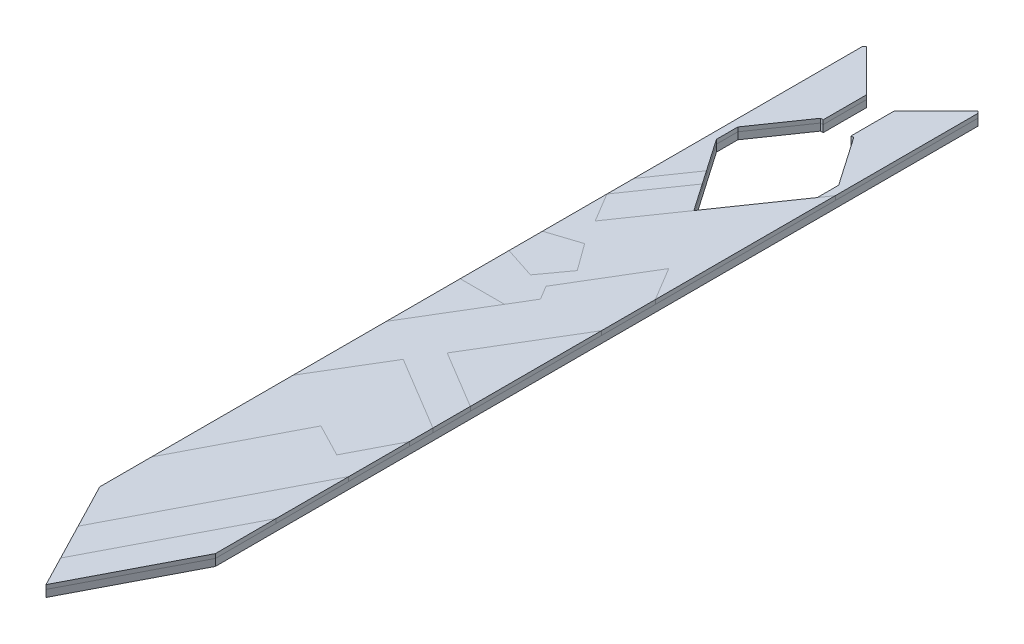
SolidWorks part; units mm, degrees
ref_plane "前视基准面" through (0, 0, 0) normal (0, 0, 1) x (1, 0, 0)
ref_plane "上视基准面" through (0, 0, 0) normal (0, 1, 0) x (1, 0, 0)
ref_plane "右视基准面" through (0, 0, 0) normal (1, 0, 0) x (0, 0, -1)
sketch "草图1" plane through (0, 0, 0) normal (0, 1, 0) x (1, 0, 0)
  line L0 (-40, 0) -> (40, 0) construction
  line L1 (40, 0) -> (0, -40)
  line L2 (0, -40) -> (-40, 0)
  line L3 (-41.46, -540.3) -> (-41.46, -1.46)
  line L4 (-41.46, -540.3) -> (0, -620.29)
  line L5 (-41.46, -1.46) -> (-40, 0)
  line L6 (0, -40) -> (0, -620.29) construction
  line L7 (0, -620.29) -> (0, -540.3) construction
  line L8 (41.46, -540.3) -> (0, -620.29)
  line L9 (41.46, -540.3) -> (41.46, -1.46)
  line L10 (41.46, -1.46) -> (40, 0)
  dimension "D1" = 80
  dimension "D2" = 40
  dimension "D4" = 580.29
  dimension "D5" = 79.99
  dimension "D6" = 82.92
extrude "凸台-拉伸1" add sketch "草图1" along normal blind 5
sketch "草图2" plane through (0, 5, 0) normal (0, 1, 0) x (1, 0, 0)
  line L0 (0, -40) -> (0, -61) construction
  line L1 (0, -61) -> (0, -163.74) construction
  line L2 (11.93, -61) -> (-11.93, -61)
  line L3 (-11.93, -61) -> (-36.16, -96.06)
  line L4 (-36.16, -96.06) -> (-36.16, -111.41)
  line L5 (-36.16, -111.41) -> (0, -163.74)
  line L6 (-36.16, -111.41) -> (36.16, -111.41) construction
  line L7 (-41.46, -1.46) -> (-41.46, -540.3) construction
  line L8 (36.16, -111.41) -> (0, -163.74)
  line L9 (36.16, -96.06) -> (36.16, -111.41)
  line L10 (11.93, -61) -> (36.16, -96.06)
  point P13 (0, -111.41)
  dimension "D1" = 21
  dimension "D2" = 102.74
  dimension "D3" = 11.93
  dimension "D4" = 15.35
  dimension "D5" = 52.33
  dimension "D6" = 5.3
extrude "切除-拉伸1" cut sketch "草图2" against normal up to next
sketch "草图3" plane through (0, 5, 0) normal (0, 1, 0) x (1, 0, 0)
  line L0 (0, -163.74) -> (0, -208.74) construction
  line L1 (0, -208.74) -> (-27, -208.74) construction
  line L2 (-27, -208.74) -> (0, -163.74)
  line L3 (27, -208.74) -> (0, -163.74)
  line L4 (27, -208.74) -> (0, -253.74)
  line L5 (-27, -208.74) -> (0, -253.74)
  line L6 (0, -263.74) -> (0, -273.74) construction
  line L7 (0, -263.74) -> (-6, -263.74) construction
  line L9 (-6, -263.74) -> (0, -273.74)
  line L10 (6, -263.74) -> (0, -273.74)
  line L12 (6, -263.74) -> (0, -253.74)
  line L13 (-6, -263.74) -> (0, -253.74)
  line L14 (0, -163.74) -> (36.16, -111.41) construction
  dimension "D1" = 45
  dimension "D2" = 27
  dimension "D3" = 10
  dimension "D4" = 6
sketch "草图4" plane through (0, 0, 0) normal (0, -1, 0) x (1, 0, 0)
  line L0 (-10, 61) -> (10, 61)
  line L1 (11.93, 61) -> (-11.93, 61) construction
  line L2 (10, 61) -> (10, 30)
  line L3 (40, 0) -> (0, 40) construction
  line L4 (10, 30) -> (-10, 30)
  line L5 (0, 30) -> (0, 61) construction
  line L6 (-10, 61) -> (-10, 30)
  dimension "D1" = 10
extrude "切除-拉伸8" cut sketch "草图4" against normal through all both
sketch "草图5" plane through (0, 0, 0) normal (0, -1, 0) x (1, 0, 0)
  line L0 (-41.46, 540.3) -> (-41.46, 548.3)
  line L1 (-41.46, 548.3) -> (0, 628.29)
  line L2 (0, 628.29) -> (0, 540.3) construction
  line L3 (-41.46, 540.3) -> (0, 620.29) construction
  line L4 (41.46, 548.3) -> (0, 628.29)
  line L5 (41.46, 540.3) -> (41.46, 548.3)
  line L6 (41.46, 540.3) -> (0, 620.29)
  line L7 (0, 620.29) -> (-41.46, 540.3)
  dimension "D1" = 8
extrude "凸台-拉伸2" add sketch "草图5" against normal up to surface (5 mm away) up to face at (0, 5, 143.6939)
sketch "草图6" plane through (0, 5, 0) normal (0, 1, 0) x (1, 0, 0)
  line L0 (0, -163.74) -> (-27, -208.74)
  line L1 (-27, -208.74) -> (0, -253.74)
  line L2 (0, -253.74) -> (27, -208.74)
  line L3 (27, -208.74) -> (0, -163.74)
  line L4 (0, -253.74) -> (-6, -263.74)
  line L5 (-6, -263.74) -> (0, -273.74)
  line L6 (0, -273.74) -> (6, -263.74)
  line L7 (6, -263.74) -> (0, -253.74)
  line L8 (0, -263.74) -> (-6, -263.74) construction
sketch "草图7" plane through (0, 0, 0) normal (0, 1, 0) x (1, 0, 0)
  line L0 (27, -208.74) -> (50, -170.4067)
  line L1 (50, 1.71) -> (-50, 1.71)
  line L2 (50, 1.71) -> (50, -628.29)
  line L3 (50, -628.29) -> (-50, -628.29)
  line L4 (-50, 1.71) -> (-50, -628.29)
  line L5 (0, -273.74) -> (-50, -357.0733)
  line L6 (0, -273.74) -> (6, -263.74) construction
  line L7 (0, -253.74) -> (27, -208.74) construction
  dimension "D1" = 100
  dimension "D2" = 630
sketch "草图8" plane through (0, 0, 0) normal (0, 1, 0) x (1, 0, 0)
  line L1 (-50, 0) -> (50, 0)
  line L2 (-50, 0) -> (-50, -640)
  line L3 (-50, -640) -> (50, -640)
  line L4 (50, 0) -> (50, -640)
  dimension "D1" = 100
  dimension "D2" = 640
sketch "草图9" plane through (0, 5, 0) normal (0, 1, 0) x (1, 0, 0)
  line L0 (6, -263.74) -> (0, -273.74)
  line L1 (-41.46, -409.7055) -> (41.46, -271.5055)
  line L3 (41.46, -452.6841) -> (-41.46, -409.7055)
  line L4 (0, -628.29) -> (0, -340.6055) construction
  line L5 (0, -163.74) -> (41.46, -103.74)
  line L7 (41.46, -184.64) -> (0, -253.74) construction
  line L9 (-41.46, -1.46) -> (-41.46, -548.3) construction
  line L10 (0, -163.74) -> (-28.9032, -205.5681)
  line L14 (0, -253.74) -> (6, -263.74)
  line L15 (27, -208.74) -> (41.46, -232.84)
  line L16 (41.46, -365.4815) -> (0, -340.6055)
  line L18 (0, -628.29) -> (41.46, -548.3)
  line L19 (41.46, -548.3) -> (41.46, -1.46)
  line L20 (41.46, -1.46) -> (40, 0)
  line L21 (40, 0) -> (10, -30)
  line L22 (10, -30) -> (10, -61)
  line L23 (10, -61) -> (11.93, -61)
  line L24 (11.93, -61) -> (36.16, -96.06)
  line L25 (36.16, -96.06) -> (36.16, -111.41)
  line L26 (36.16, -111.41) -> (0, -163.74)
  line L27 (0, -163.74) -> (-36.16, -111.41)
  line L28 (-36.16, -111.41) -> (-36.16, -96.06)
  line L29 (-36.16, -96.06) -> (-11.93, -61)
  line L30 (-11.93, -61) -> (-10, -61)
  line L31 (-10, -61) -> (-10, -30)
  line L32 (-10, -30) -> (-40, 0)
  line L33 (-40, 0) -> (-41.46, -1.46)
  line L34 (-41.46, -1.46) -> (-41.46, -548.3)
  line L35 (-41.46, -548.3) -> (0, -628.29)
  line L36 (0, -628.29) -> (41.46, -548.3)
  line L37 (41.46, -548.3) -> (41.46, -1.46)
  line L38 (41.46, -1.46) -> (40, 0)
  line L39 (40, 0) -> (10, -30)
  line L40 (10, -30) -> (10, -61)
  line L41 (10, -61) -> (11.93, -61)
  line L42 (11.93, -61) -> (36.16, -96.06)
  line L43 (36.16, -96.06) -> (36.16, -111.41)
  line L44 (36.16, -111.41) -> (0, -163.74)
  line L45 (0, -163.74) -> (-36.16, -111.41)
  line L46 (-36.16, -111.41) -> (-36.16, -96.06)
  line L47 (-36.16, -96.06) -> (-11.93, -61)
  line L48 (-11.93, -61) -> (-10, -61)
  line L49 (-10, -61) -> (-10, -30)
  line L50 (-10, -30) -> (-40, 0)
  line L51 (-40, 0) -> (-41.46, -1.46)
  line L52 (-41.46, -1.46) -> (-41.46, -548.3)
  line L53 (-41.46, -548.3) -> (0, -628.29)
  line L55 (-41.46, -184.64) -> (-13.5091, -144.19)
  line L56 (-18.6346, -262.2564) -> (-4.5278, -242.84)
  line L57 (-4.5278, -242.84) -> (-18.6346, -223.4236)
  line L58 (-18.6346, -223.4236) -> (-41.46, -230.84)
  line L59 (-41.46, -230.84) -> (-41.46, -254.84)
  line L60 (-41.46, -254.84) -> (-18.6346, -262.2564)
  line L62 (-41.46, -165.2902) -> (-20.1944, -134.5151)
  line L63 (-27, -208.74) -> (0, -253.74) construction
  line L64 (-9.66, -289.84) -> (-41.46, -289.84)
  line L65 (-28.9032, -205.5681) -> (-41.46, -184.64)
  line L66 (-28.9032, -205.5681) -> (-18.6346, -223.4236)
  line L67 (41.46, -409.2224) -> (-36.043, -558.7512)
  line L70 (0, -431.1948) -> (-41.46, -511.1848)
  line L71 (-41.46, -511.1848) -> (21.3079, -543.7183) construction
  line L72 (-11.2634, -606.5591) -> (41.46, -504.8382)
  line L78 (41.46, -548.3) -> (41.46, -1.46) construction
  line L80 (0, -628.29) -> (0, -532.6741) construction
  line L83 (-24.7796, -580.4821) -> (0, -532.6741)
  line L84 (0, -532.6741) -> (41.46, -452.6841)
  line L95 (-11.8334, -360.3278) -> (41.46, -392.3038)
  line L99 (27, -208.74) -> (41.46, -184.64)
  line L150 (27, -208.74) -> (0, -253.74) construction
  line L151 (0, -273.74) -> (-41.46, -342.84)
  line L152 (6, -263.74) -> (0, -273.74) construction
  line L153 (27, -208.74) -> (0, -163.74)
  line L184 (0, -273.74) -> (-6, -263.74)
  line L185 (-6, -263.74) -> (27, -208.74)
  circle A0 centre (-24.9434, -242.84) radius 16.5166 construction
  line M1 (0, -628.29) -> (41.46, -548.3)
  line M2 (41.46, -548.3) -> (41.46, -1.46)
  line M3 (41.46, -1.46) -> (40, 0)
  line M4 (40, 0) -> (10, -30)
  line M5 (10, -30) -> (10, -61)
  line M6 (10, -61) -> (11.93, -61)
  line M7 (11.93, -61) -> (36.16, -96.06)
  line M8 (36.16, -96.06) -> (36.16, -111.41)
  line M9 (36.16, -111.41) -> (0, -163.74)
  line M10 (0, -163.74) -> (-36.16, -111.41)
  line M11 (-36.16, -111.41) -> (-36.16, -96.06)
  line M12 (-36.16, -96.06) -> (-11.93, -61)
  line M13 (-11.93, -61) -> (-10, -61)
  line M14 (-10, -61) -> (-10, -30)
  line M15 (-10, -30) -> (-40, 0)
  line M16 (-40, 0) -> (-41.46, -1.46)
  line M17 (-41.46, -1.46) -> (-41.46, -548.3)
  line M18 (-41.46, -548.3) -> (0, -628.29)
  dimension "D2" = 20
  dimension "D3" = 53
  dimension "D4" = 11
  dimension "D5" = 23
  dimension "D6" = 24
  dimension "D7" = 24
  dimension "D8" = 20
  dimension "D9" = 35
  dimension "D1" = 0
extrude "凸台-拉伸8" add sketch "草图9" along normal blind 3 separate body contours L5 M8 M2 M3 M4 M5 M6 M7 | L52 L60 L56 L57 L58 | L151 L64 L52 | L65 M10 M11 M12 M13 M14 M15 M16 M17 | L65 L55 M10 region at (-30.86, 5, 307.5067) region at (-20.9317, 5, 174.591) region at (-24.9434, 5, 242.84) region at (28.8954, 5, 49.413) region at (-30.1781, 5, 69.3465)
extrude "凸台-拉伸9" add sketch "草图9<7>" along normal blind 3 separate body contours L151 L52 | L72 L53 M1 M2 region at (-30.86, 5, 307.5067) region at (17.8019, 5, 571.3471)
sketch "草图9<7>" plane through (0, 5, 0) normal (0, 1, 0) x (1, 0, 0) same geometry as "草图9"
extrude "凸台-拉伸12" add sketch "草图9<12>" along normal blind 3 separate body contours L83 L72 L71 M18 | L153 L99 L37 L5 M9 | L99 L15 M2 | L66 L65 L52 L58 | L52 L55 L45 | L95 L1 L67 L37 | L70 M17 | L16 L1 M2 | L184 L185 L153 L66 L57 L56 L60 L52 L64 L151 region at (-7.7004, 5, 229.6871) region at (36.64, 5, 208.74) region at (26.2926, 5, 160.4905) region at (3.5384, 5, 402.4621) region at (-27.64, 5, 450.695) region at (27.64, 5, 325.8641) region at (-33.8149, 5, 212.8942) region at (-29.0802, 5, 157.4874) region at (11.5913, 5, 535.4002)
sketch "草图9<12>" plane through (0, 5, 0) normal (0, 1, 0) x (1, 0, 0) same geometry as "草图9"
extrude "凸台-拉伸14" add sketch "草图9<17>" along normal blind 3 separate body contours L70 L52 L67 M18 | L67 L37 | L83 L84 L67 L53 | L1 L95 L16 M2 | L185 L14 L0 L151 L52 L1 L15 M2 | L185 L184 L0 L14 region at (0.721, 5, 302.5199) region at (0, 5, 263.74) region at (17.6485, 5, 365.164) region at (-13.8935, 5, 488.7875) region at (35.5411, 5, 435.129) region at (1.2099, 5, 508.9824)
sketch "草图9<17>" plane through (0, 5, 0) normal (0, 1, 0) x (1, 0, 0) same geometry as "草图9"
